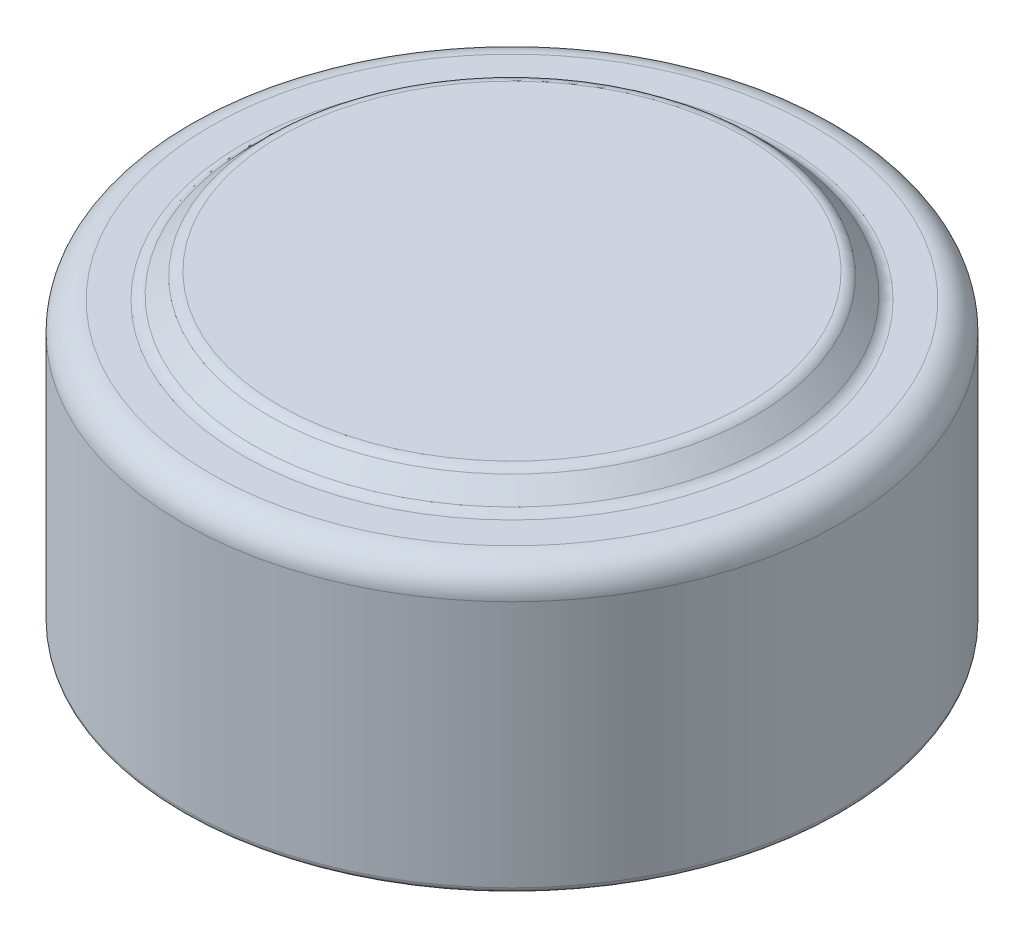
SolidWorks part; units mm, degrees
ref_plane "Front Plane" through (0, 0, 0) normal (0, 0, 1) x (1, 0, 0)
ref_plane "Top Plane" through (0, 0, 0) normal (0, 1, 0) x (1, 0, 0)
ref_plane "Right Plane" through (0, 0, 0) normal (1, 0, 0) x (0, 0, -1)
sketch "Sketch1" plane through (0, 0, 0) normal (0, 0, 1) x (1, 0, 0)
  line L0 (0, 0) -> (-5.7, 0)
  line L1 (-5.8, 0.1) -> (-5.8, 4.46)
  line L2 (-4.0964, 5.4) -> (0, 5.4)
  line L3 (0, 5.4) -> (0, 0)
  line L4 (-4.2732, 5.3268) -> (-4.5668, 5.0332)
  line L7 (-5.3, 4.96) -> (-4.7436, 4.96)
  arc A0 (-5.8, 4.46) -> (-5.3, 4.96) centre (-5.3, 4.46) cw
  arc A1 (-4.0964, 5.4) -> (-4.2732, 5.3268) centre (-4.0964, 5.15) ccw
  arc A2 (-4.7436, 4.96) -> (-4.5668, 5.0332) centre (-4.7436, 5.21) ccw
  arc A3 (-5.7, 0) -> (-5.8, 0.1) centre (-5.7, 0.1) cw
  point P9 (-5.8, 4.96)
  point P14 (-4.64, 4.96)
  point P17 (-5.8, 0)
  dimension "D6" = 0.5
  dimension "D7" = 0.25
  dimension "D8" = 0.1
  dimension "D1" = 5.8
  dimension "D2" = 5.4
  dimension "D3" = 4.64
  dimension "D4" = 4.96
  dimension "D5" = 45
revolve "Revolve1" add sketch "Sketch1" angle 360 about L3
sketch "Sketch2" plane through (0, 0, 0) normal (0, -1, 0) x (1, 0, 0)
  line L0 (0.295, -0.25) -> (0.295, -2)
  line L1 (-0.205, 2) -> (0.295, 2)
  line L2 (-0.205, 2) -> (-0.205, 0.25)
  line L3 (-0.205, -2) -> (0.295, -2)
  line L4 (0.295, 2) -> (0.295, 0.25)
  line L5 (-2, 0.25) -> (-0.205, 0.25)
  line L6 (-2, 0.25) -> (-2, -0.25)
  line L7 (-2, -0.25) -> (-0.205, -0.25)
  line L8 (2, 0.25) -> (2, -0.25)
  line L9 (-0.205, -0.25) -> (-0.205, -2)
  line L10 (0.295, 0.25) -> (2, 0.25)
  line L11 (0.295, -0.25) -> (2, -0.25)
  circle A0 centre (0, 0) radius 4 construction
  text T0 "                                SR44" font "Century Gothic" height 1
  dimension "D1" = 8
  dimension "D2" = 0.5
  dimension "D3" = 0.25
  dimension "D4" = 0.205
  dimension "D5" = 0.5
  dimension "D6" = 4
  dimension "D7" = 2
  dimension "D8" = 2
  dimension "D9" = 4
wrap "Wrap1" sketch "Sketch2" wrap type scribe source sketch "Sketch2" face at (0, 0, 5.7)
